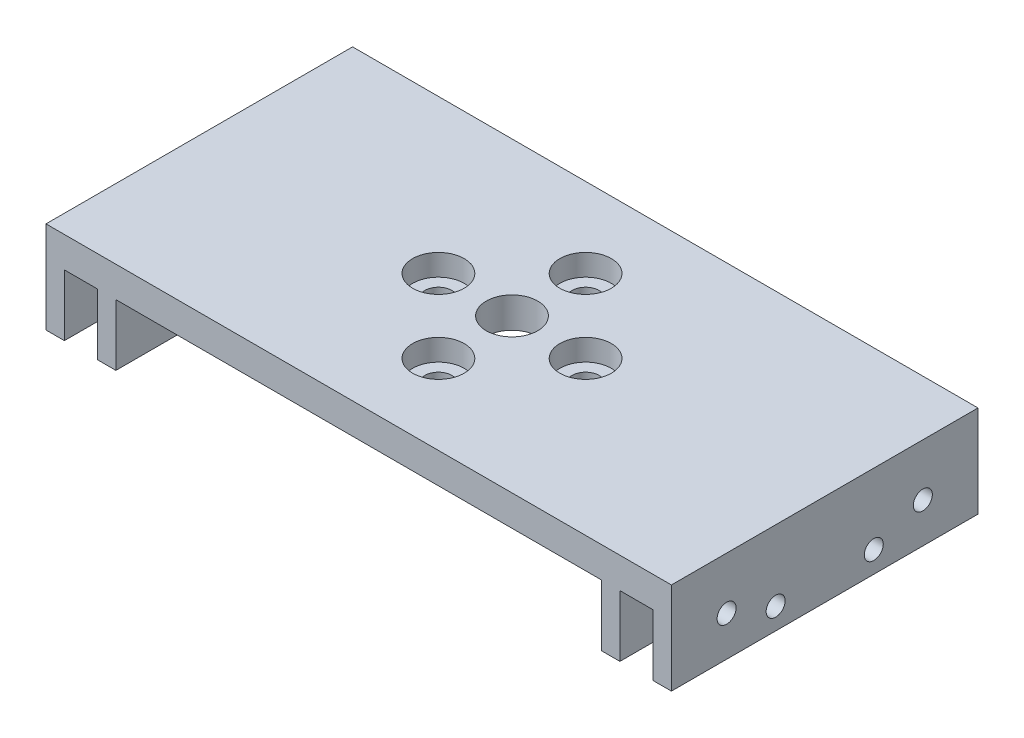
SolidWorks part; units mm, degrees
ref_plane "Front Plane" through (0, 0, 0) normal (0, 0, 1) x (1, 0, 0)
ref_plane "Top Plane" through (0, 0, 0) normal (0, 1, 0) x (1, 0, 0)
ref_plane "Right Plane" through (0, 0, 0) normal (1, 0, 0) x (0, 0, -1)
sketch "Sketch4" plane through (0, 0, 0) normal (0, 1, 0) x (1, 0, 0)
  line L1 (-51, 25) -> (51, 25)
  line L2 (-51, 25) -> (-51, -25)
  line L3 (-51, -25) -> (51, -25)
  line L4 (51, 25) -> (51, -25)
  line L5 (-51, 25) -> (51, -25) construction
  line L6 (-51, -25) -> (51, 25) construction
  circle A1 centre (0, 0) radius 4.2
  circle A2 centre (0, 0) radius 12 construction
  circle A3 centre (0, -12) radius 2.2
  circle A4 centre (-12, 0) radius 2.2
  circle A5 centre (0, 12) radius 2.2
  circle A6 centre (12, 0) radius 2.2
  point P18 (0, 0)
  dimension "D1" = 4
extrude "Boss-Extrude3" add sketch "Sketch4" against normal blind 5
sketch "Sketch16" plane through (0, -5, 0) normal (0, -1, 0) x (1, 0, 0)
  line L0 (0, 0) -> (42.6, 0) construction
  line L6 (0, 0) -> (-42.6, 0) construction
  line L12 (-42.6, -25) -> (-42.6, 25)
  line L13 (-42.6, 25) -> (-39.6, 25)
  line L14 (-39.6, 25) -> (-39.6, -25)
  line L15 (-39.6, -25) -> (-42.6, -25)
  line L16 (-42.6, 0) -> (-48, 0) construction
  line L17 (-48, -25) -> (-48, 25)
  line L18 (-48, 25) -> (-51, 25)
  line L19 (-51, 25) -> (-51, -25)
  line L20 (-51, -25) -> (-48, -25)
  line L21 (42.6, -25) -> (42.6, 25)
  line L22 (42.6, 25) -> (39.6, 25)
  line L23 (39.6, 25) -> (39.6, -25)
  line L24 (39.6, -25) -> (42.6, -25)
  line L25 (42.6, 0) -> (48, 0) construction
  line L26 (48, -25) -> (48, 25)
  line L27 (48, 25) -> (51, 25)
  line L28 (51, 25) -> (51, -25)
  line L29 (51, -25) -> (48, -25)
  point P7 (-42.6, 0)
  point P14 (-48, 0)
  point P19 (42.6, 0)
  point P25 (48, 0)
extrude "Boss-Extrude4" add sketch "Sketch16" along normal blind 10
sketch "Sketch17" plane through (-51, 0, 0) normal (-1, 0, 0) x (0, 0, 1)
  line L0 (-25, -15) -> (-25, -11.5) construction
  line L1 (-25, -15) -> (-25, 0) construction
  line L2 (-25, -11.5) -> (-8, -11.5) construction
  line L3 (-8, -11.5) -> (8, -11.5) construction
  line L4 (-16, -8.5) -> (16, -8.5) construction
  line L5 (-25, 0) -> (-25, -8.5) construction
  line L6 (-25, -8.5) -> (-16, -8.5) construction
  circle A0 centre (-16, -8.5) radius 1.55
  circle A1 centre (-8, -11.5) radius 1.55
  circle A3 centre (8, -11.5) radius 1.55
  circle A5 centre (16, -8.5) radius 1.55
extrude "Cut-Extrude10" cut sketch "Sketch17" against normal up to surface (11.4 mm away) up to face at (-39.6, -10, 0)
sketch "Sketch18" plane through (51, 0, 0) normal (1, 0, 0) x (0, 0, -1)
  line L0 (-25, -15) -> (-25, -11.5) construction
  line L1 (-25, -11.5) -> (-8, -11.5) construction
  line L2 (-8, -11.5) -> (8, -11.5) construction
  line L3 (8, -11.5) -> (-8, -11.5) construction
  line L4 (-25, 0) -> (-25, -8.5) construction
  line L5 (-25, -15) -> (-25, 0) construction
  line L6 (-25, -8.5) -> (-16, -8.5) construction
  line L10 (16, -8.5) -> (-16, -8.5) construction
  circle A0 centre (-8, -11.5) radius 1.55
  circle A1 centre (8, -11.5) radius 1.55
  circle A2 centre (16, -8.5) radius 1.55
  circle A3 centre (-16, -8.5) radius 1.55
extrude "Cut-Extrude11" cut sketch "Sketch18" against normal up to surface (11.4 mm away) up to face at (39.6, -10, 0)
sketch "Sketch19" plane through (0, 0, 0) normal (0, 1, 0) x (1, 0, 0)
  circle A0 centre (0, 0) radius 12 construction
  circle A1 centre (0, 12) radius 4.2
  circle A2 centre (12, 0) radius 4.2
  circle A3 centre (0, -12) radius 4.2
  circle A4 centre (-12, 0) radius 4.2
  point P14 (0, 0)
  dimension "D1" = 4
extrude "Cut-Extrude12" cut sketch "Sketch19" against normal blind 3.5
